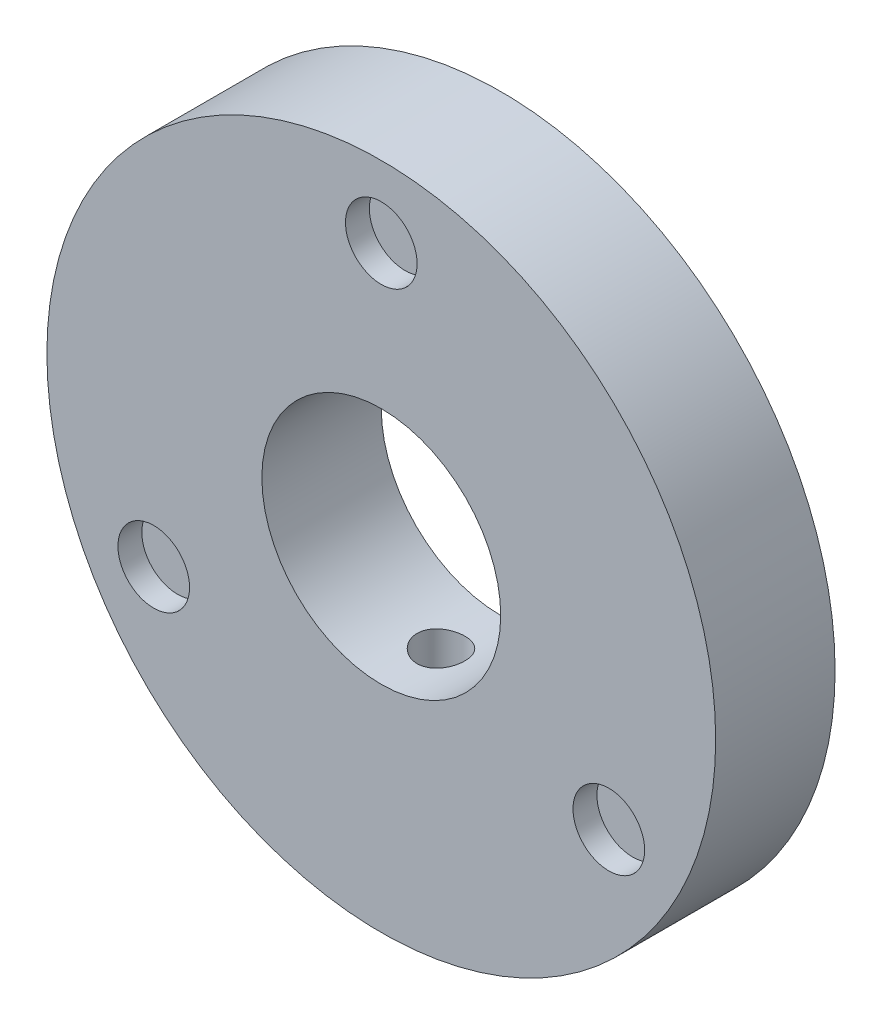
SolidWorks part; units mm, degrees
ref_plane "Front Plane" through (0, 0, 0) normal (0, 0, 1) x (1, 0, 0)
ref_plane "Top Plane" through (0, 0, 0) normal (0, 1, 0) x (1, 0, 0)
ref_plane "Right Plane" through (0, 0, 0) normal (1, 0, 0) x (0, 0, -1)
sketch "Sketch3" plane through (0, 0, 0) normal (0, 0, 1) x (1, 0, 0)
  circle A0 centre (0, 0) radius 14
  circle A1 centre (0, 0) radius 5
  dimension "D1" = 10
  dimension "D2" = 28
extrude "Boss-Extrude1" add sketch "Sketch3" along normal blind 5
sketch "Sketch4" plane through (0, 0, 5) normal (0, 0, 1) x (1, 0, 0)
  circle A1 centre (0, 0) radius 11 construction
  circle A3 centre (0, 11) radius 1.5
  circle A4 centre (9.5263, -5.5) radius 1.5
  circle A5 centre (-9.5263, -5.5) radius 1.5
  point P4 (-6.7923, 8.6525)
  point P8 (0, 0)
  point P10 (0, 0)
  point P12 (13.7673, -4.4648)
  point P13 (0, 0)
  dimension "D1" = 3
  dimension "D2" = 3
  dimension "D3" = 22
extrude "Cut-Extrude1" cut sketch "Sketch4" against normal blind 1
sketch "Sketch5" plane through (0, 0, 0) normal (0, 0, -1) x (-1, 0, 0)
  circle A0 centre (0, 0) radius 11 construction
  circle A2 centre (0, 11) radius 1.5
  circle A3 centre (9.5263, -5.5) radius 1.5
  circle A4 centre (-9.5263, -5.5) radius 1.5
  point P2 (-4.2334, 8.9476)
  point P3 (0, 0)
  point P4 (-8.4245, -7.8838)
  point P5 (0, 0)
  point P15 (0, 0)
  dimension "D1" = 3
  dimension "D2" = 3
  dimension "D3" = 22
extrude "Cut-Extrude2" cut sketch "Sketch5" against normal blind 1 contours A2 | A3 | A4
sketch "Sketch6" plane through (0, 0, 0) normal (0, 1, 0) x (1, 0, 0)
  circle A0 centre (0, -2.5) radius 1
  point P2 (0, 0)
  dimension "D2" = 2
  dimension "D1" = 2.5
extrude "Cut-Extrude3" cut sketch "Sketch6" against normal blind 30
